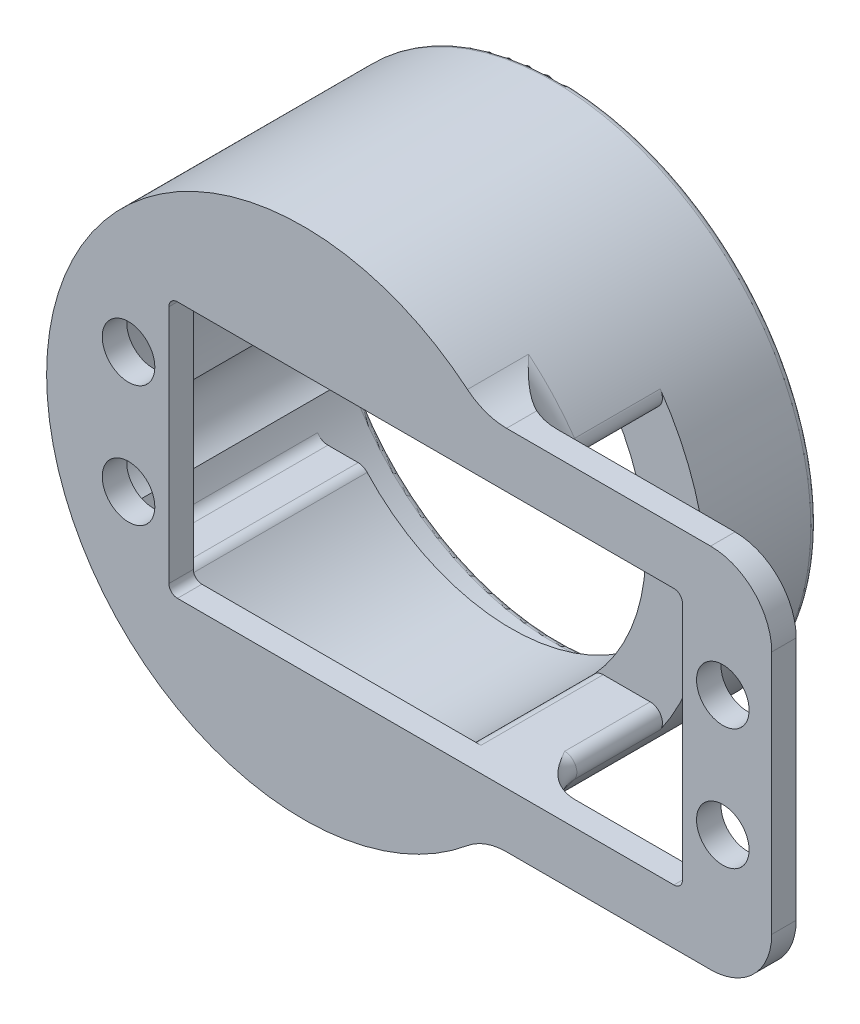
SolidWorks part; units mm, degrees
ref_plane "前视基准面" through (0, 0, 0) normal (0, 0, 1) x (1, 0, 0)
ref_plane "上视基准面" through (0, 0, 0) normal (0, 1, 0) x (1, 0, 0)
ref_plane "右视基准面" through (0, 0, 0) normal (1, 0, 0) x (0, 0, -1)
sketch "草图1" plane through (0, 0, 0) normal (0, 0, 1) x (1, 0, 0)
  line L0 (0, 10.5) -> (42, 10.5) construction
  line L1 (0, 0) -> (42, 0)
  line L2 (0, 0) -> (0, 21)
  line L3 (0, 21) -> (42, 21)
  line L4 (42, 0) -> (42, 21)
  line L5 (21, 21) -> (21, 0) construction
  line L6 (0, 10.5) -> (-16.1185, 10.5) construction
  line L7 (11, 25.5) -> (49.3, 25.5)
  line L8 (49.3, 25.5) -> (49.3, -4.5)
  line L9 (49.3, -4.5) -> (11, -4.5)
  line L10 (0, 21) -> (-4.2315, 21)
  line L11 (0, 0) -> (-4.2315, 0)
  circle A0 centre (-3.3, 15.45) radius 2.15
  circle A1 centre (-3.3, 5.55) radius 2.15
  circle A2 centre (45.3, 5.55) radius 2.15
  circle A3 centre (45.3, 15.45) radius 2.15
  circle A4 centre (11, 10.5) radius 15
  circle A5 centre (11, 10.5) radius 18.5
  circle A6 centre (11, 10.5) radius 21
  dimension "D3" = 4.3
  dimension "D6" = 30
  dimension "D8" = 37
  dimension "D11" = 42
  dimension "D1" = 42
  dimension "D2" = 21
  dimension "D4" = 24.3
  dimension "D5" = 4.95
  dimension "D7" = 14.3
  dimension "D9" = 90
  dimension "D10" = 4
extrude "凸台-拉伸2" add sketch "草图1" along normal blind 2 contours A6 L3 L4 L1 L9 L8 L7 A3 A2 | L3 A6 L7 A5 | L3 A5 L7 A4 | L9 A5 L1 A4 | L9 A6 L1 A5 | L1 A4 | L11 A5 L9 A4 L1 | L7 A6 L9 A5 | L7 A5 L10 L3 A4 | L10 A5 L11 L2 A4 A1 A0 | L2 A4 A0 A1 | L3 A4 region at (-4.5848, 10.5, 0) region at (7.622, -4.755, 0) region at (11, -1.8254, 0) region at (-1.4022, 10.5, 0) region at (7.7582, -8.2734, 0) region at (20.9458, -2.5053, 0) region at (7.622, 25.755, 0) region at (25.856, -2.3497, 0) region at (11, 22.8254, 0) region at (20.9458, 23.5053, 0) region at (25.856, 23.3497, 0) region at (27.8966, -2.6028, 0)
fillet "圆角1" radius 5 4 edges at (25.6969, 25.5, 1) (25.6969, -4.5, 1) (49.3, -4.5, 1) (49.3, 25.5, 1)
fillet "圆角2" radius 0.7 4 edges at (42, 0, 1) (42, 21, 1) (0, 0, 1) (0, 21, 1)
sketch "草图3" plane through (0, 0, 0) normal (0, 0, -1) x (-1, 0, 0)
  line L0 (-0.7, 0) -> (-41.3, 0) construction
  line L1 (-0.7, 0) -> (-41.3, 0)
  line L2 (-0.7, 21) -> (-41.3, 21) construction
  line L3 (-49.3, 20.5) -> (-49.3, 0.5)
  line L4 (-44.3, -4.5) -> (-27.6132, -4.5)
  line L5 (-27.6132, 25.5) -> (-44.3, 25.5)
  line L6 (-49.3, 20.5) -> (-49.3, 0.5)
  line L7 (-44.3, -4.5) -> (-27.6132, -4.5)
  line L8 (-27.6132, 25.5) -> (-44.3, 25.5)
  line L9 (-0.7, 21) -> (-41.3, 21)
  line L10 (-0.7, 0) -> (1.0727, 0)
  line L11 (-0.7, 21) -> (1.0727, 21)
  line L12 (-21, 0) -> (4.5342, 0)
  line L13 (-21, 21) -> (4.4259, 21.1586)
  circle A0 centre (-11, 10.5) radius 16
  circle A1 centre (-11, 10.5) radius 18.75
  arc A5 (-49.3, 0.5) -> (-44.3, -4.5) centre (-44.3, 0.5) ccw
  arc A6 (-24.4184, -5.6538) -> (-27.6132, -4.5) centre (-27.6132, -9.5) ccw
  arc A7 (-24.4184, -5.6538) -> (-24.4184, 26.6538) centre (-11, 10.5) ccw
  arc A8 (-27.6132, 25.5) -> (-24.4184, 26.6538) centre (-27.6132, 30.5) ccw
  arc A9 (-44.3, 25.5) -> (-49.3, 20.5) centre (-44.3, 20.5) ccw
  arc A10 (-49.3, 0.5) -> (-44.3, -4.5) centre (-44.3, 0.5) ccw
  arc A11 (-24.4184, -5.6538) -> (-27.6132, -4.5) centre (-27.6132, -9.5) ccw
  arc A12 (-24.4184, -5.6538) -> (-24.4184, 26.6538) centre (-11, 10.5) ccw
  arc A13 (-27.6132, 25.5) -> (-24.4184, 26.6538) centre (-27.6132, 30.5) ccw
  arc A14 (-44.3, 25.5) -> (-49.3, 20.5) centre (-44.3, 20.5) ccw
  line M13 (-0.7, 0) -> (-41.3, 0)
  dimension "D2" = 32
  dimension "D3" = 37.5
  dimension "D4" = 0
  dimension "D1" = 0
extrude "凸台-拉伸3" add sketch "草图3" along normal blind 15 contours A1 L12 A0 M13 | L13 A1 L9 A0 region at (-2.8035, -0.3215, 0) region at (24.8035, 21.3204, 0)
sketch "草图4" plane through (0, 0, 0) normal (0, 0, -1) x (-1, 0, 0)
  line L0 (4.5342, 0) -> (-26.5342, 0)
  line L1 (-26.5342, 0) -> (7.1865, 0)
  line L2 (-26.5342, 21) -> (7.086, 21.1722)
  line L3 (-49.3, 20.5) -> (-49.3, 0.5)
  line L4 (-44.3, -4.5) -> (-27.6132, -4.5)
  line L5 (-27.6132, 25.5) -> (-44.3, 25.5)
  line L6 (-49.3, 20.5) -> (-49.3, 0.5)
  line L7 (-44.3, -4.5) -> (-27.6132, -4.5)
  line L8 (-27.6132, 25.5) -> (-44.3, 25.5)
  line L9 (-26.5342, 0) -> (-29.1865, 0)
  line L10 (-26.5342, 21) -> (-29.1944, 20.9864)
  arc A0 (-26.5342, 0) -> (4.5342, 0) centre (-11, 10.5) ccw construction
  arc A1 (-26.5342, 0) -> (4.5342, 0) centre (-11, 10.5) ccw
  circle A2 centre (-11, 10.5) radius 18.75
  arc A3 (4.4259, 21.1586) -> (-26.5342, 21) centre (-11, 10.5) ccw construction
  arc A4 (4.4259, 21.1586) -> (-26.5342, 21) centre (-11, 10.5) ccw
  arc A5 (-49.3, 0.5) -> (-44.3, -4.5) centre (-44.3, 0.5) ccw
  arc A6 (-24.4184, -5.6538) -> (-27.6132, -4.5) centre (-27.6132, -9.5) ccw
  arc A7 (-24.4184, -5.6538) -> (-24.4184, 26.6538) centre (-11, 10.5) ccw
  arc A8 (-27.6132, 25.5) -> (-24.4184, 26.6538) centre (-27.6132, 30.5) ccw
  arc A9 (-44.3, 25.5) -> (-49.3, 20.5) centre (-44.3, 20.5) ccw
  arc A10 (-49.3, 0.5) -> (-44.3, -4.5) centre (-44.3, 0.5) ccw
  arc A11 (-24.4184, -5.6538) -> (-27.6132, -4.5) centre (-27.6132, -9.5) ccw
  arc A12 (-24.4184, -5.6538) -> (-24.4184, 26.6538) centre (-11, 10.5) ccw
  arc A13 (-27.6132, 25.5) -> (-24.4184, 26.6538) centre (-27.6132, 30.5) ccw
  arc A14 (-44.3, 25.5) -> (-49.3, 20.5) centre (-44.3, 20.5) ccw
  circle A15 centre (-11, 10.5) radius 21
  point P21 (-29.1865, 21)
  arc M13 (-26.5342, 21) -> (4.4259, 21.1586) centre (-11, 10.5) cw
  arc M23 (4.5342, 0) -> (-26.5342, 0) centre (-11, 10.5) cw
  line M24 (-26.5342, 0) -> (-41.3, 0)
  line M28 (-41.3, 21) -> (-26.5342, 21)
  arc M35 (-24.4184, -5.6538) -> (-24.4184, 26.6538) centre (-11, 10.5) ccw
  dimension "D1" = 0
extrude "凸台-拉伸4" add sketch "草图4" along normal blind 19 contours A15 L1 M24 M35 M23 | A2 L1 L2 M35 | A15 L2 M35 M28 M13 region at (-7.8424, 10.5927, 0) region at (-5.8604, -0.3786, 0) region at (27.8604, 21.3776, 0)
sketch "草图5" plane through (0, 0, 0) normal (0, 0, -1) x (-1, 0, 0)
  line L5 (4.4259, 21.1586) -> (0.9523, 21.1369)
  line L6 (-23.0727, 21) -> (-0.7, 21)
  line L7 (0, 20.3) -> (0, 0.7)
  line L8 (-0.7, 0) -> (-23.0727, 0)
  line L9 (1.0727, 0) -> (4.5342, 0)
  line L10 (4.4259, 21.1586) -> (0.9523, 21.1369)
  line L11 (-23.0727, 21) -> (-0.7, 21)
  line L12 (0, 20.3) -> (0, 0.7)
  line L13 (-0.7, 0) -> (-23.0727, 0)
  line L14 (1.0727, 0) -> (4.5342, 0)
  circle A0 centre (3.3, 5.55) radius 2.15 construction
  circle A1 centre (3.3, 5.55) radius 2.15
  circle A2 centre (3.3, 15.45) radius 2.15 construction
  circle A3 centre (3.3, 15.45) radius 2.15
  circle A4 centre (3.3, 5.55) radius 4.25
  arc A5 (4.5342, 0) -> (4.4259, 21.1586) centre (-11, 10.5) ccw
  arc A6 (0.9523, 21.1369) -> (-23.0727, 21) centre (-11, 10.5) ccw
  arc A7 (0, 20.3) -> (-0.7, 21) centre (-0.7, 20.3) ccw
  arc A8 (-0.7, 0) -> (0, 0.7) centre (-0.7, 0.7) ccw
  arc A9 (-23.0727, 0) -> (1.0727, 0) centre (-11, 10.5) ccw
  arc A10 (4.5342, 0) -> (4.4259, 21.1586) centre (-11, 10.5) ccw
  arc A11 (0.9523, 21.1369) -> (-23.0727, 21) centre (-11, 10.5) ccw
  arc A12 (0, 20.3) -> (-0.7, 21) centre (-0.7, 20.3) ccw
  arc A13 (-0.7, 0) -> (0, 0.7) centre (-0.7, 0.7) ccw
  arc A14 (-23.0727, 0) -> (1.0727, 0) centre (-11, 10.5) ccw
  circle A15 centre (3.3, 15.45) radius 4.25
  arc M15 (4.5342, 0) -> (4.4259, 21.1586) centre (-11, 10.5) ccw
  dimension "D2" = 8.5
  dimension "D3" = 8.5
  dimension "D1" = 0
extrude "切除-拉伸1" cut sketch "草图5" along normal blind 50 contours A4 M15 | A10 A15 region at (-6.9282, 16.7059, 0) region at (-6.9282, 4.2941, 0)
sketch "草图6" plane through (0, 0, -15) normal (0, 0, -1) x (-1, 0, 0)
  line L2 (-23.0727, 0) -> (-26.5342, 0)
  line L3 (4.5342, 0) -> (1.0727, 0)
  line L4 (-23.0727, 0) -> (-26.5342, 0)
  line L5 (4.5342, 0) -> (1.0727, 0)
  line L6 (0.9523, 21.1369) -> (4.4259, 21.1586)
  line L7 (-26.5342, 21) -> (-23.0727, 21)
  line L8 (0.9523, 21.1369) -> (4.4259, 21.1586)
  line L9 (-26.5342, 21) -> (-23.0727, 21)
  circle A0 centre (-11, 10.5) radius 16
  circle A1 centre (-11, 10.5) radius 18.75
  arc A2 (-26.5342, 0) -> (4.5342, 0) centre (-11, 10.5) ccw
  arc A3 (-23.0727, 0) -> (1.0727, 0) centre (-11, 10.5) ccw
  arc A4 (-26.5342, 0) -> (4.5342, 0) centre (-11, 10.5) ccw
  arc A5 (-23.0727, 0) -> (1.0727, 0) centre (-11, 10.5) ccw
  arc A6 (4.4259, 21.1586) -> (-26.5342, 21) centre (-11, 10.5) ccw
  arc A7 (0.9523, 21.1369) -> (-23.0727, 21) centre (-11, 10.5) ccw
  arc A8 (4.4259, 21.1586) -> (-26.5342, 21) centre (-11, 10.5) ccw
  arc A9 (0.9523, 21.1369) -> (-23.0727, 21) centre (-11, 10.5) ccw
  line M11 (-23.0727, 0) -> (-26.5342, 0)
  dimension "D1" = 0
  dimension "D2" = 0
extrude "凸台-拉伸5" add sketch "草图6" against normal blind 5 contours L9 A1 A0 M11 region at (27.1695, 10.5, -15)
sketch "草图7" plane through (0, 0, -19) normal (0, 0, -1) x (-1, 0, 0)
  line L2 (-26.5342, 0) -> (-29.1865, 0)
  line L3 (-29.1865, 21) -> (-26.5342, 21)
  line L4 (-26.5342, 0) -> (-29.1865, 0)
  line L5 (-29.1865, 21) -> (-26.5342, 21)
  circle A0 centre (-11, 10.5) radius 18.75
  circle A1 centre (-11, 10.5) radius 21
  arc A6 (7.3736, 6.7618) -> (7.3736, 14.2382) centre (-11, 10.5) ccw
  arc A7 (5.7526, 2.0791) -> (7.3736, 6.7618) centre (3.3, 5.55) ccw
  arc A8 (-26.5342, 0) -> (5.7526, 2.0791) centre (-11, 10.5) ccw
  arc A9 (-29.1865, 0) -> (-29.1865, 21) centre (-11, 10.5) ccw
  arc A10 (5.7526, 18.9209) -> (-26.5342, 21) centre (-11, 10.5) ccw
  arc A11 (7.3736, 14.2382) -> (5.7526, 18.9209) centre (3.3, 15.45) ccw
  arc A12 (7.3736, 6.7618) -> (7.3736, 14.2382) centre (-11, 10.5) ccw
  arc A13 (5.7526, 2.0791) -> (7.3736, 6.7618) centre (3.3, 5.55) ccw
  arc A14 (-26.5342, 0) -> (5.7526, 2.0791) centre (-11, 10.5) ccw
  arc A15 (-29.1865, 0) -> (-29.1865, 21) centre (-11, 10.5) ccw
  arc A16 (5.7526, 18.9209) -> (-26.5342, 21) centre (-11, 10.5) ccw
  arc A17 (7.3736, 14.2382) -> (5.7526, 18.9209) centre (3.3, 15.45) ccw
  line M13 (-26.5342, 0) -> (-29.1865, 0)
  line M15 (-29.1865, 21) -> (-26.5342, 21)
  dimension "D1" = 0
extrude "凸台-拉伸6" add sketch "草图7" against normal blind 9 contours A1 A0 M15 M13 region at (29.8602, 10.5, -19)
fillet "圆角3" radius 1 8 edges at (-1.0727, 0, -7.5) (-4.5342, 0, -7.5) (-0.9523, 21.1369, -7.5) (-4.4259, 21.1586, -7.5) (23.0727, 21, -5) (23.0727, 0, -5) (29.1865, 21, -5) (29.1865, 0, -5)
fillet "圆角4" radius 3 4 edges at (28.2505, -0.539, 0) (28.2505, 21.539, 0) (26.4351, -3.7393, 0) (26.4351, 24.7393, 0)
fillet "圆角5" radius 0.5 2 edges at (-10, 10.5, -19) (29.75, 10.5, -19)
